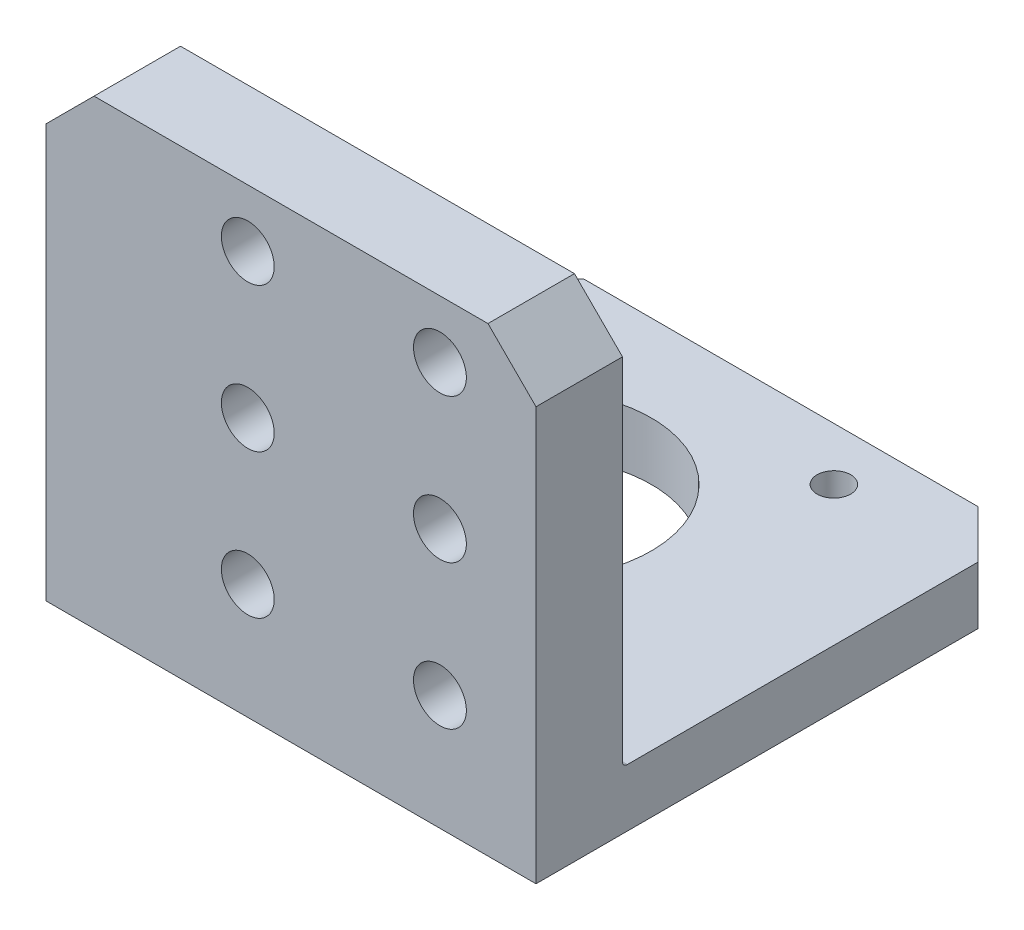
SolidWorks part; units mm, degrees
ref_plane "前基準面" through (0, 0, 0) normal (0, 0, 1) x (1, 0, 0)
ref_plane "上基準面" through (0, 0, 0) normal (0, 1, 0) x (1, 0, 0)
ref_plane "右基準面" through (0, 0, 0) normal (1, 0, 0) x (0, 0, -1)
sketch "草圖1" plane through (0, 0, 0) normal (0, 0, 1) x (1, 0, 0)
  line L0 (30, 21) -> (21, 21)
  line L1 (-21, 21) -> (21, 21)
  line L2 (-21, 21) -> (-21, -21)
  line L3 (-21, -21) -> (21, -21)
  line L4 (30, -21) -> (21, -21)
  line L9 (30, 21) -> (30, -21)
  circle A0 centre (0, 15) radius 2.75
  circle A1 centre (20, 15) radius 2.75
  circle A2 centre (20, 0) radius 2.75
  circle A3 centre (20, -15) radius 2.75
  circle A4 centre (0, 0) radius 2.75
  circle A5 centre (0, -15) radius 2.75
  point P4 (0, 21)
  point P6 (-21, 0)
  dimension "D3" = 5.5
  dimension "D4" = 6
  dimension "D7" = 6
  dimension "D1" = 42
  dimension "D2" = 42
  dimension "D5" = 2
  dimension "D10" = 10
  dimension "D6" = 3
extrude "填料-伸長1" add sketch "草圖1" along normal blind 9
sketch "草圖3" plane through (0, -21, 0) normal (0, -1, 0) x (1, 0, 0)
  line L1 (-21, 9) -> (21, 9)
  line L2 (-21, 9) -> (-21, 51)
  line L3 (-21, 51) -> (21, 51)
  line L4 (21, 9) -> (21, 51)
  line L6 (0, 51) -> (0, 9) construction
  line L7 (-21, 30) -> (21, 30) construction
  circle A0 centre (-15.5, 45.5) radius 1.75
  circle A1 centre (-15.5, 14.5) radius 1.75
  circle A2 centre (15.5, 14.5) radius 1.75
  circle A3 centre (15.5, 45.5) radius 1.75
  circle A4 centre (0, 30) radius 12
  dimension "D3" = 3.5
  dimension "D6" = 24
  dimension "D1" = 42
  dimension "D2" = 42
  dimension "D4" = 5.5
  dimension "D5" = 5.5
extrude "填料-伸長2" add sketch "草圖3" along normal blind 6 separate body
sketch "草圖4" plane through (0, -27, 0) normal (0, -1, 0) x (1, 0, 0)
  line L0 (0, 51) -> (0, 9) construction
  line L1 (21, 51) -> (-21, 51) construction
  line L3 (0, 9) -> (21, 30) construction
  line L4 (21, 9) -> (21, 51) construction
  line L5 (21, 30) -> (-21, 30) construction
  line L6 (-21, 51) -> (-21, 9) construction
  circle A0 centre (-15.5, 45.5) radius 3
  circle A1 centre (-15.5, 14.5) radius 3
  circle A2 centre (15.5, 14.5) radius 3
  circle A3 centre (15.5, 45.5) radius 3
  dimension "D1" = 6
extrude "除料-伸長2" cut sketch "草圖4" against normal blind 3
sketch "草圖5" plane through (0, -21, 0) normal (0, -1, 0) x (1, 0, 0)
  line L0 (-21, 0) -> (30, 0) construction
  line L1 (-21, 9) -> (21, 9)
  line L2 (-21, 9) -> (-21, 0)
  line L3 (-21, 0) -> (21, 0)
  line L4 (21, 9) -> (21, 0)
extrude "填料-伸長3" add sketch "草圖5" along normal up to surface (6 mm away) up to face at (-15.5, -27, 17.5)
sketch "草圖6" plane through (0, 0, 9) normal (0, 0, 1) x (1, 0, 0)
  circle A0 centre (0, 15) radius 4.25
  circle A1 centre (20, 15) radius 4.25
  circle A2 centre (20, 0) radius 4.25
  circle A3 centre (20, -15) radius 4.25
  circle A4 centre (0, 0) radius 4.25
  circle A5 centre (0, -15) radius 4.25
  dimension "D1" = 8.5
  dimension "D2" = 2
  dimension "D3" = 3
extrude "除料-伸長3" cut sketch "草圖6" against normal blind 5
chamfer "導角2" distance 5 angle 45 2 edges at (-21, 21, 4.5) (30, 21, 4.5)
sketch "草圖7" plane through (21, 0, 0) normal (1, 0, 0) x (0, 0, -1)
  line L1 (-51, -27) -> (0, -27)
  line L2 (-51, -27) -> (-51, -21)
  line L3 (-51, -21) -> (0, -21)
  line L4 (0, -27) -> (0, -21)
extrude "填料-伸長4" add sketch "草圖7" along normal up to surface (9 mm away) up to face at (30, -2.5, 4.5)
chamfer "導角3" distance 5 angle 45 2 edges at (-21, -24, 51) (30, -24, 51)
fillet "圓角1" radius 0.5 1 edges at (4.5, -21, 9)
mirror "鏡射1" about plane through (0, 0, 0) normal (0, 0, 1) of "圓角1", "導角3", "填料-伸長4", "導角2", "除料-伸長3", "填料-伸長3", "除料-伸長2", "填料-伸長2", "填料-伸長1"
sketch "草圖8" plane through (0, 21, 0) normal (0, 1, 0) x (1, 0, 0)
  line L0 (30, 9) -> (30, -9) construction
  line L1 (30, 0) -> (-21, 0)
  line L2 (30, 0) -> (30, -51)
  line L3 (30, -51) -> (-21, -51)
  line L4 (-21, 0) -> (-21, -51)
extrude "除料-伸長4" cut sketch "草圖8" against normal through all
